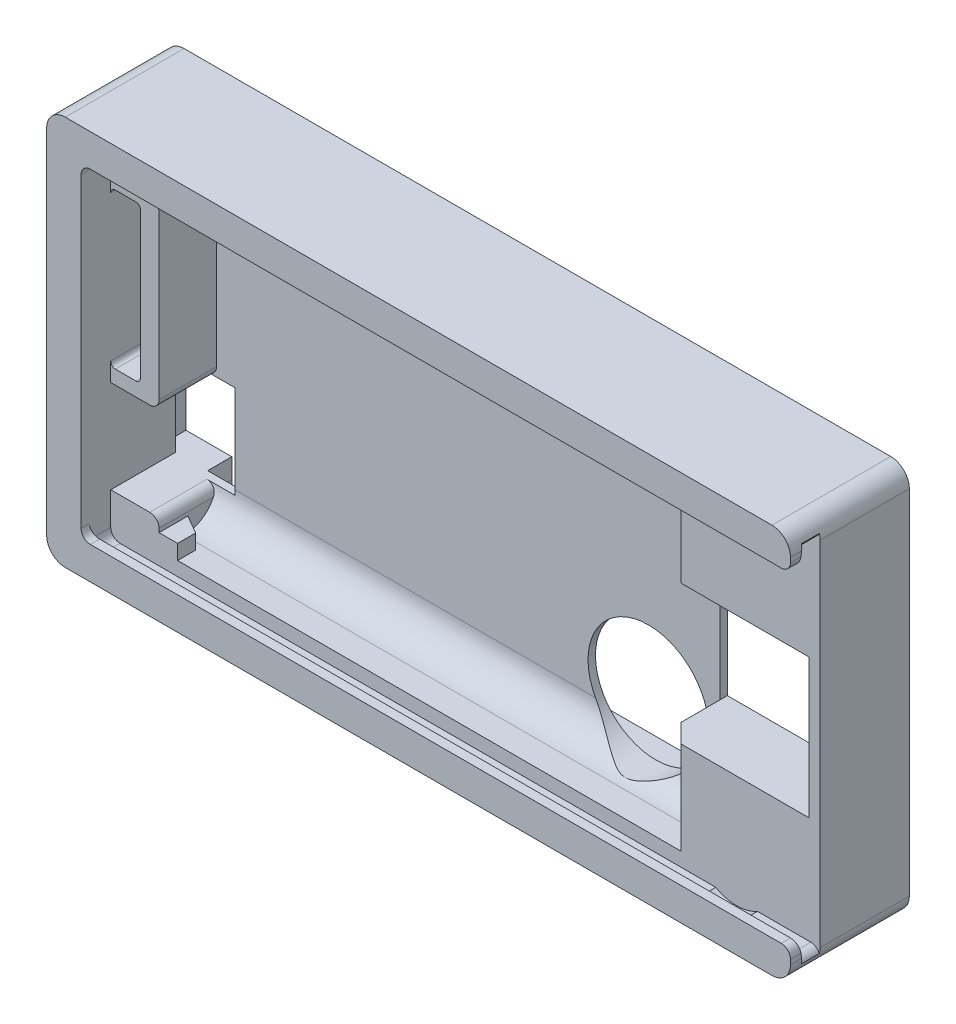
SolidWorks part; units mm, degrees
ref_plane "Front Plane" through (0, 0, 0) normal (0, 0, 1) x (1, 0, 0)
ref_plane "Top Plane" through (0, 0, 0) normal (0, 1, 0) x (1, 0, 0)
ref_plane "Right Plane" through (0, 0, 0) normal (1, 0, 0) x (0, 0, -1)
sketch "Sketch1" plane through (0, 0, 0) normal (0, 0, 1) x (1, 0, 0)
  line L1 (-26.5, 17) -> (26.5, 17)
  line L2 (-26.5, 17) -> (-26.5, -17)
  line L3 (-26.5, -17) -> (26.5, -17)
  line L4 (26.5, 17) -> (26.5, -17)
  line L5 (-26.5, 17) -> (26.5, -17) construction
  line L6 (-26.5, -17) -> (26.5, 17) construction
  point P0 (0, 0)
  dimension "D1" = 34
  dimension "D2" = 53
sketch "Sketch2" plane through (0, 0, 0) normal (0, 0, 1) x (1, 0, 0)
  line L1 (-32.3, 19) -> (44.1, 19)
  line L2 (-32.3, 19) -> (-32.3, -19)
  line L3 (-32.3, -19) -> (44.1, -19)
  line L4 (44.1, 19) -> (44.1, -19)
  line L6 (-26.5, 17) -> (-26.5, -17) construction
  line L7 (26.5, 17) -> (26.5, -17) construction
  line L8 (-26.5, -17) -> (-26.5, -19) construction
  line L9 (-26.5, 17) -> (-26.5, 19) construction
  line L10 (-26.5, 17) -> (26.5, 17) construction
  dimension "D1" = 5.8
  dimension "D2" = 17.6
  dimension "D3" = 2
extrude "Boss-Extrude1" add sketch "Sketch2" along normal blind 7
sketch "Sketch3" plane through (0, 0, 0) normal (1, 0, 0) x (0, 0, -1)
  line L0 (-7.3, 17) -> (-4.3, 17) construction
  line L1 (-1.3, 0) -> (-7.3, 0) construction
  line L2 (-7.3, -17) -> (-7.3, 17) construction
  line L3 (-1.3, -14) -> (-1.3, 14) construction
  line L4 (-7.3, -17) -> (-4.3, -17) construction
  line L5 (-7.8, 17.5) -> (-4.3, 17.5)
  line L6 (-0.8, -14) -> (-0.8, 14)
  line L7 (-7.8, -17.5) -> (-4.3, -17.5)
  line L8 (-7.8, -17.5) -> (-7.8, 17.5)
  arc A0 (-4.3, 17) -> (-1.3, 14) centre (-4.3, 14) cw construction
  arc A1 (-4.3, -17) -> (-1.3, -14) centre (-4.3, -14) ccw construction
  arc A2 (-4.3, 17.5) -> (-0.8, 14) centre (-4.3, 14) cw
  arc A3 (-4.3, -17.5) -> (-0.8, -14) centre (-4.3, -14) ccw
  dimension "D1" = 3
  dimension "D2" = 6
  dimension "D3" = 34
  dimension "D5" = 0.8
  dimension "D4" = 0.5
extrude "Cut-Battery" cut sketch "Sketch3" against normal mid plane 54.2
sketch "Sketch4" plane through (0, 0, 7) normal (0, 0, 1) x (1, 0, 0)
  line L1 (0, 0) -> (34, 0) construction
  line L2 (40.9, 7.5) -> (27.1, 7.5)
  line L3 (40.9, 7.5) -> (40.9, -7.5)
  line L4 (40.9, -7.5) -> (27.1, -7.5)
  line L7 (27.1, 7.5) -> (27.1, -7.5)
  line L8 (40.9, 7.5) -> (27.1, -7.5) construction
  line L9 (40.9, -7.5) -> (27.1, 7.5) construction
  line L10 (27.1, -14) -> (27.1, 14) construction
  line L12 (27.1, 17.5) -> (27.1, -17.5) construction
  line L13 (44.1, -19) -> (44.1, 19) construction
  point P0 (34, 0)
  dimension "D1" = 15
  dimension "D2" = 3.2
extrude "Cut for finger" cut sketch "Sketch4" against normal through all
chamfer "Chamfer3" distance 2 distance2 7 1 edges at (40.9, 0, 7) first distance on face at (17, 0, 7)
sketch "Sketch5" plane through (0, 17.5, 0) normal (0, -1, 0) x (1, 0, 0)
  line L0 (-27.1, 7) -> (-25.1, 7)
  line L1 (27.1, 7) -> (-27.1, 7) construction
  line L2 (-25.1, 7) -> (-25.1, 3.9)
  line L3 (-25.1, 3.9) -> (-27.1, 3.9)
  line L4 (-27.1, 3.9) -> (-27.1, 7)
  line L5 (-26.9, 3.8) -> (-24.9, 3.8) construction
  line L6 (-24.9, 3.8) -> (-24.9, 6.8) construction
  line L7 (-24.9, 6.8) -> (-20.5432, 6.8) construction
  line L8 (-26.9, 3.8) -> (-26.9, 0.8) construction
  line L9 (-26.9, 0.8) -> (-20.5432, 0.8) construction
  line L10 (-20.5432, 0.8) -> (-20.5432, 6.8) construction
  line L11 (-27.1, 0.8) -> (27.1, 0.8) construction
  line L12 (-27.1, 0.8) -> (-27.1, 4.3) construction
  dimension "D1" = 6
  dimension "D2" = 3
  dimension "D3" = 0.2
  dimension "D4" = 2
  dimension "D5" = 0.2
  dimension "D6" = 0.1
extrude "Boss-Extrude2" add sketch "Sketch5" along normal blind 1.6
chamfer "Chamfer1" distance 2 angle 30 1 edges at (-25.1, 16.6885, 3.9) first distance on face at (-26.1, 16.6885, 3.9)
mirror "Mirror1" about plane through (0, 0, 0) normal (0, 1, 0) of "Chamfer1", "Boss-Extrude2"
sketch "Sketch6" plane through (0, 0, 7) normal (0, 0, 1) x (1, 0, 0)
  line L1 (-32.3, -4.5) -> (-25.1, -4.5)
  line L2 (-32.3, -4.5) -> (-32.3, -14.5)
  line L3 (-32.3, -14.5) -> (-25.1, -14.5)
  line L4 (-25.1, -4.5) -> (-25.1, -14.5)
  line L7 (-26.5, -17) -> (26.5, -17) construction
  line L8 (-32.3, 19) -> (-32.3, -19) construction
  point P8 (-32.3, -9.5)
  dimension "D1" = 10
  dimension "D2" = 7.5
  dimension "D3" = 7.2
extrude "Cut-Connector" cut sketch "Sketch6" against normal through all
sketch "Sketch9" plane through (0, 0, 0) normal (0, 0, 1) x (1, 0, 0)
  line L0 (44.1, -19) -> (-32.3, -19)
  line L1 (-32.3, -19) -> (-32.3, 19)
  line L2 (-32.3, 19) -> (44.1, 19)
  line L3 (44.1, 19) -> (44.1, 21)
  line L4 (44.1, 21) -> (-34.3, 21)
  line L5 (-34.3, 21) -> (-34.3, -21)
  line L6 (-34.3, -21) -> (44.1, -21)
  line L7 (44.1, -21) -> (44.1, -19)
  line L8 (44.1, -19) -> (44.1, 19) construction
  dimension "D1" = 2
  dimension "D2" = 2
extrude "Boss-Extrude3" add sketch "Sketch9" along normal offset from surface (10.2 mm away) 3.2 up to face at (-2.78, -1.9, 7) offset beyond the face yes
sketch "Sketch10" plane through (0, 0, 7) normal (0, 0, 1) x (1, 0, 0)
  line L0 (44.1, 19) -> (44.1, 21) construction
  line L1 (13.6743, 19.6) -> (35.1, 19.6) construction
  line L3 (-32.3, 19) -> (44.1, 19) construction
  line L4 (0, 0) -> (44.1, 0) construction
  line L5 (44.1, -19) -> (44.1, 19) construction
  circle A0 centre (35.1, 15.1) radius 4.5
  circle A1 centre (35.1, -15.1) radius 4.5
  dimension "D1" = 9
  dimension "D2" = 9
  dimension "D3" = 0.6
  dimension "D4" = 15.1
extrude "Cut-Latch" cut sketch "Sketch10" along normal blind 2
sketch "Sketch11" plane through (44.1, 0, 0) normal (1, 0, 0) x (0, 0, -1)
  line L0 (-10.2, 19) -> (-9, 19)
  line L1 (-10.2, 19) -> (-7, 19) construction
  line L2 (-9, 19) -> (-9.2, 17.5)
  line L3 (-9.2, 17.5) -> (-10.2, 17.5)
  line L4 (-10.2, -19) -> (-10.2, 19) construction
  line L5 (-10.2, 17.5) -> (-10.2, 19)
  line L8 (0, 0) -> (-12.817, 0) construction
  line L9 (-9.2, -17.5) -> (-10.2, -17.5)
  line L10 (-9, -19) -> (-9.2, -17.5)
  line L11 (-10.2, -19) -> (-9, -19)
  line L12 (-10.2, -17.5) -> (-10.2, -19)
  dimension "D1" = 1
  dimension "D2" = 38
  dimension "D3" = 82.405
  dimension "D4" = 1.5
  dimension "D5" = 1.2
extrude "Boss-Extrude4" add sketch "Sketch11" against normal up to surface (76.4 mm away) up to face at (-32.3, -4.75, 6.05)
fillet "Fillet3" radius 1 2 edges at (44.1, -19, 8) (44.1, 19, 8)
chamfer "Chamfer2" distance 2 angle 45 2 edges at (27.1, -12.5, 7) (27.1, 12.5, 7)
fillet "Fillet2" radius 1 2 edges at (-27.1, -14.5, 3.9179) (-27.1, -4.5, 3.9)
sketch "Sketch12" plane through (0, 0, 7) normal (0, 0, 1) x (1, 0, 0)
  line L0 (-28.1, -4.5) -> (-32.3, -4.5) construction
  line L1 (-32.3, 13.7) -> (-29.1, 13.7)
  line L2 (-32.3, 13.7) -> (-32.3, -3)
  line L3 (-32.3, -3) -> (-29.1, -3)
  line L4 (-29.1, 13.7) -> (-29.1, -3)
  line L5 (-27.1, -3.5) -> (-27.1, 14) construction
  line L6 (-32.3, 19) -> (-32.3, -4.5) construction
  dimension "D1" = 1.5
  dimension "D2" = 2
  dimension "D3" = 3.2
  dimension "D4" = 16.7
extrude "Cut-Extrude6" cut sketch "Sketch12" against normal through all
fillet "Fillet1" radius 0.5 4 edges at (-29.1, 13.7, 3.5) (-32.3, 13.7, 3.5) (-32.3, -3, 3.5) (-29.1, -3, 3.5)
sketch "Sketch13" plane through (0, 0, 0) normal (0, 0, -1) x (-1, 0, 0)
  line L0 (33.8, 17.35) -> (33.8, -17.35) construction
  line L1 (34.3, 21) -> (36, 21)
  line L2 (34.3, 21) -> (34.3, -21)
  line L3 (34.3, -21) -> (36, -21)
  line L4 (36, 21) -> (36, -21)
  dimension "D1" = 2.2
extrude "Boss-Extrude5" add sketch "Sketch13" against normal up to surface (10.2 mm away) up to face at (5.4, 0, 10.2)
sketch "Sketch16" plane through (0, 0, 0) normal (0, 0, -1) x (-1, 0, 0)
  circle A0 centre (-39.55, 16.4) radius 1.1
  circle A1 centre (31.45, 16.4) radius 1.1
  circle A2 centre (31.45, -16.4) radius 1.1
  circle A3 centre (-39.55, -16.4) radius 1.1
  circle A4 centre (-39.55, 16.4) radius 1.25 construction
  circle A5 centre (31.45, 16.4) radius 1.25 construction
  circle A6 centre (31.45, -16.4) radius 1.25 construction
  circle A7 centre (-39.55, -16.4) radius 1.25 construction
  dimension "D1" = 2.2
extrude "Cut-Extrude7" cut sketch "Sketch16" against normal offset from surface (3 mm away) 4 up to face at (-3.3881, -0.3944, 7)
sketch "Sketch18" plane through (0, 0, 0) normal (0, 0, -1) x (-1, 0, 0)
  line L0 (-35.9671, 17.75) -> (27.8671, 17.75)
  line L1 (-41.9, 18.75) -> (33.8, 18.75)
  line L2 (-41.9, 18.75) -> (-41.9, -18.75)
  line L3 (-41.9, -18.75) -> (33.8, -18.75)
  line L4 (33.8, 18.75) -> (33.8, -18.75)
  line L5 (-40.9, 12.8171) -> (-40.9, -12.8171)
  line L6 (-41.9, 14.178) -> (-40.9, 14.178) construction
  line L7 (-37.328, 17.75) -> (-37.328, 18.75) construction
  line L8 (-41.9, 0) -> (33.8, 0) construction
  line L9 (-4.05, 18.75) -> (-4.05, -18.75) construction
  line L10 (-35.9671, -17.75) -> (27.8671, -17.75)
  line L11 (32.8, 12.8171) -> (32.8, -12.8171)
  line L12 (28.8623, -16.6528) -> (28.8623, -14.5)
  line L13 (32.3, -14.5) -> (25.1, -14.5) construction
  line L14 (28.8623, -14.5) -> (32.8, -14.5)
  line L15 (32.8, -14.5) -> (32.8, -12.8171)
  line L16 (-40.5, 18.75) -> (32.4, 18.75) construction
  line L17 (-41.9, -17.35) -> (-41.9, 17.35) construction
  line L18 (33.8, 17.35) -> (33.8, -17.35) construction
  line L19 (32.4, -18.75) -> (21.5, -18.75) construction
  arc A0 (-36.9623, 16.6528) -> (-39.8028, 13.8123) centre (-39.55, 16.4) cw
  arc A1 (-36.9623, 16.6528) -> (-35.9671, 17.75) centre (-35.9671, 16.75) cw
  arc A2 (-39.8028, 13.8123) -> (-40.9, 12.8171) centre (-39.9, 12.8171) ccw
  circle A3 centre (-39.55, 16.4) radius 1.1
  circle A4 centre (-39.55, 16.4) radius 1.1 construction
  circle A5 centre (-39.55, -16.4) radius 1.1
  arc A6 (-39.8028, -13.8123) -> (-40.9, -12.8171) centre (-39.9, -12.8171) cw
  arc A7 (-36.9623, -16.6528) -> (-35.9671, -17.75) centre (-35.9671, -16.75) ccw
  arc A8 (-36.9623, -16.6528) -> (-39.8028, -13.8123) centre (-39.55, -16.4) ccw
  arc A10 (28.8623, -16.6528) -> (27.8671, -17.75) centre (27.8671, -16.75) cw
  circle A12 centre (31.45, -16.4) radius 1.1
  circle A13 centre (31.45, 16.4) radius 1.1
  arc A14 (31.7028, 13.8123) -> (32.8, 12.8171) centre (31.8, 12.8171) cw
  arc A15 (28.8623, 16.6528) -> (27.8671, 17.75) centre (27.8671, 16.75) ccw
  arc A16 (28.8623, 16.6528) -> (31.7028, 13.8123) centre (31.45, 16.4) ccw
  point P36 (-40.9, 0)
  point P38 (-4.05, 17.75)
  point P39 (-4.05, -17.75)
  point P53 (32.8, 0)
  dimension "D2" = 2.6
  dimension "D3" = 1
  dimension "D1" = 1
extrude "PCB stand" add sketch "Sketch18" along normal blind 2.6
sketch "Sketch19" plane through (0, 0, -2.6) normal (0, 0, -1) x (-1, 0, 0)
  line L0 (33.8, -18.75) -> (33.8, 18.75) construction
  line L1 (32.8, -14.5) -> (33.8, -14.5)
  line L2 (32.8, -14.5) -> (32.8, -4.5)
  line L3 (32.8, -4.5) -> (33.8, -4.5)
  line L4 (33.8, -14.5) -> (33.8, -4.5)
  line L5 (25.1, -4.5) -> (32.3, -4.5) construction
extrude "Cut-Extrude8" cut sketch "Sketch19" against normal up to surface (2.6 mm away) up to face at (-30.7, 5.35, 0)
hole_wizard "Ø2.0mm Dowel Hole1" positions "Sketch20" profile "Sketch21" hole size "Ø2.0" standard "DIN"
sketch "Sketch20" plane through (0, 0, -2.6) normal (0, 0, -1) x (-1, 0, 0)
  point P0 (-39.55, -16.4)
  point P3 (-39.55, 16.4)
  point P6 (31.45, 16.4)
  point P9 (31.45, -16.4)
sketch "Sketch21" plane through (39.55, -16.4, -2.6) normal (1, 0, 0) x (0, 1, 0)
  line L0 (0, 0) -> (0, 9.4053)
  line L1 (0, 9.4053) -> (1.1, 7.5)
  line L2 (1.1, 7.5) -> (1.1, 0)
  line L5 (1.1, 0) -> (0, 0)
  line L10 (0, 9.4053) -> (-1.1, 7.5) construction
  line L11 (0, -6.35) -> (0, 107.95) construction
  dimension "Hole Dia." = 2.2
  dimension "Hole Depth" = 7.5
  dimension "Drill Angle" = 60
sketch "Sketch22" plane through (0, 0, 0) normal (0, 0, -1) x (-1, 0, 0)
  line L1 (36, -21) -> (-44.1, -21)
  line L2 (36, -21) -> (36, 21)
  line L3 (36, 21) -> (-44.1, 21)
  line L4 (-44.1, -21) -> (-44.1, 21)
  line L5 (-41.9, 18.75) -> (33.8, 18.75)
  line L6 (-41.9, 18.75) -> (-41.9, -18.75)
  line L7 (-41.9, -18.75) -> (33.8, -18.75)
  line L8 (33.8, 18.75) -> (33.8, -18.75)
extrude "Boss-Extrude8" add sketch "Sketch22" along normal up to surface (2.6 mm away) up to face at (0.7177, -0.5363, -2.6)
fillet "Fillet4" radius 2 4 edges at (44.1, 21, 3.8) (44.1, -21, 3.8) (-36, -21, 3.8) (-36, 21, 3.8)
fillet "Fillet5" radius 1 2 edges at (44.1, -17.5, 9.7) (44.1, 17.5, 9.7)
fillet "Fillet6" radius 1 2 edges at (-32.3, 17.5, 9.7) (-32.3, -17.5, 9.7)
fillet "Fillet7" radius 1 2 edges at (-32.3, -19, 8) (-32.3, 19, 8)
sketch "Sketch23" plane through (0, 0, -2.6) normal (0, 0, -1) x (-1, 0, 0)
  line L0 (8.5, -18.75) -> (8.5, -13.1) construction
  line L1 (8.5, -14.55) -> (21.5, -14.55)
  line L2 (8.5, -14.55) -> (8.5, -18.75)
  line L3 (8.5, -18.75) -> (21.5, -18.75)
  line L4 (21.5, -14.55) -> (21.5, -18.75)
  point P6 (8.5, -13.811)
  point P9 (8.5, -14.672)
  dimension "D1" = 4.2
extrude "Cut-Capacitor" cut sketch "Sketch23" against normal blind 3
fillet "Fillet8" radius 2.2 1 edges at (-15, -18.75, 0.4)
sketch "Sketch24" plane through (0, 0, -2.6) normal (0, 0, -1) x (-1, 0, 0)
  circle A0 centre (-19.4, -10.85) radius 6.5
  circle A1 centre (-19.4, -10.85) radius 6 construction
  dimension "D1" = 0.5
extrude "Motor" cut sketch "Sketch24" against normal up to surface (9.6 mm away) up to face at (-2.429, -0.355, 7)
equation "\"D1@Cut-Battery\" = 53 / 2 + 0.6"
